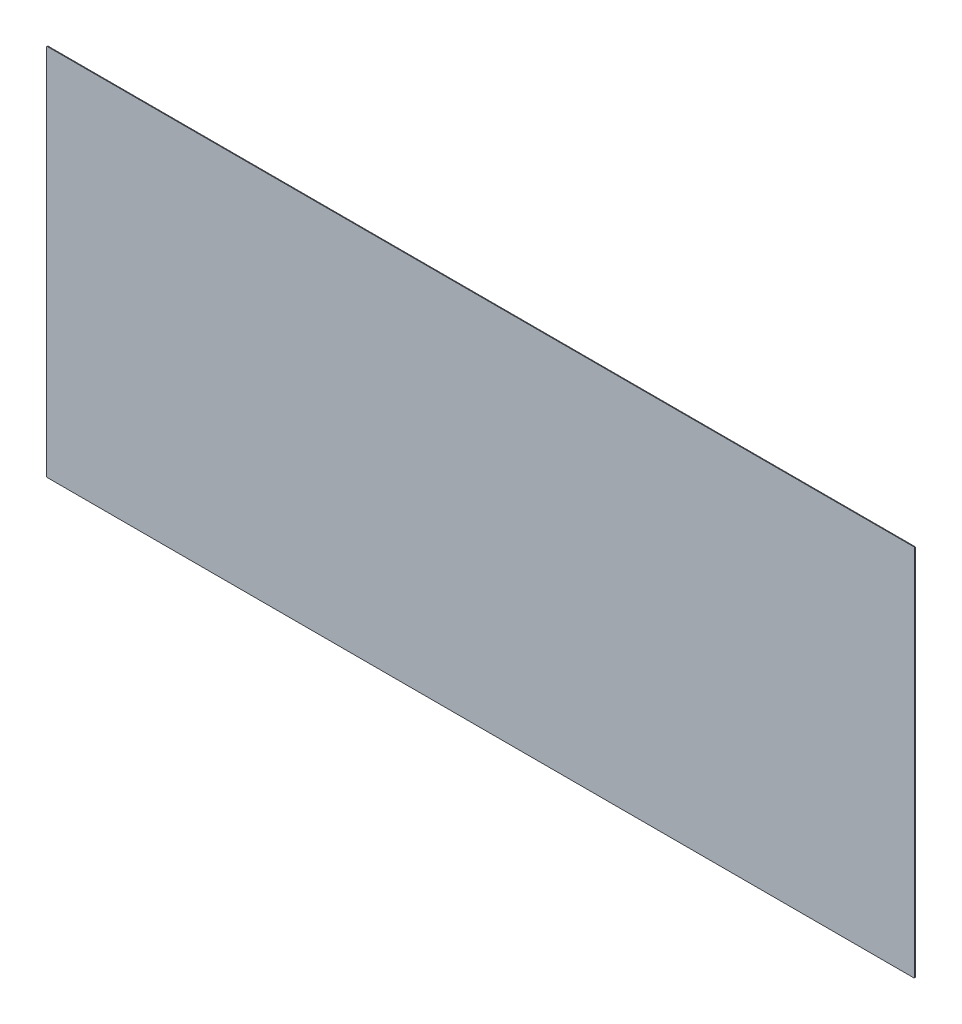
SolidWorks part; units mm, degrees
ref_plane "Front Plane" through (0, 0, 0) normal (0, 0, 1) x (1, 0, 0)
ref_plane "Top Plane" through (0, 0, 0) normal (0, 1, 0) x (1, 0, 0)
ref_plane "Right Plane" through (0, 0, 0) normal (1, 0, 0) x (0, 0, -1)
sketch "Sketch1" plane through (0, 0, 0) normal (0, 0, 1) x (1, 0, 0)
  line L1 (1, 0) -> (1159, 0)
  line L2 (0, 1) -> (0, 498)
  line L3 (1, 499) -> (1159, 499)
  line L4 (1160, 1) -> (1160, 498)
  arc A0 (1159, 499) -> (1160, 498) centre (1159, 498) cw
  arc A1 (1159, 0) -> (1160, 1) centre (1159, 1) ccw
  arc A2 (1, 0) -> (0, 1) centre (1, 1) cw
  arc A3 (0, 498) -> (1, 499) centre (1, 498) cw
  point P7 (1160, 499)
  point P10 (1160, 0)
  point P13 (0, 0)
  point P16 (0, 499)
  dimension "D3" = 1
  dimension "D1" = 1160
  dimension "D2" = 499
base flange "Base-Flange1" sketch "Sketch1" thickness 1 reverse thickness direction no parameters "D1"=2
sketch "Bend-Lines1" [suppressed] plane through (0, 0, 0) normal (0, 1, 0) x (1, 0, 0)
sketch "Bounding-Box1" [suppressed] plane through (0, 0, 0) normal (0, 1, 0) x (1, 0, 0)
sheet metal parameters "Sheet-Metal1" thickness 1 parameters "D1"=2
flat pattern "Flat-Pattern1" [suppressed]
sketch "Bend-Lines2" plane through (0, 0, 0) normal (0, 1, 0) x (1, 0, 0)
sketch3d "Bounding-Box2" [suppressed]
  line L0 (-1159, -498, 0) -> (1, -498, 0) construction
  line L1 (-1159, 1, 0) -> (1, 1, 0) construction
  line L2 (-1159, -498, 0) -> (-1159, 1, 0) construction
  line L3 (1, -498, 0) -> (1, 1, 0) construction
